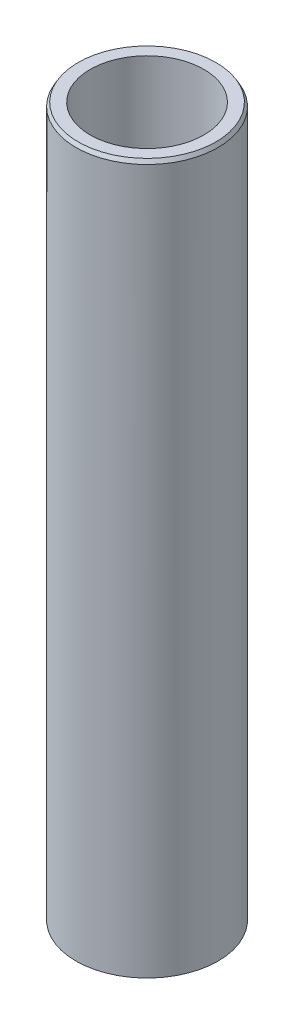
SolidWorks part; units mm, degrees
ref_plane "Front Plane" through (0, 0, 0) normal (0, 0, 1) x (1, 0, 0)
ref_plane "Top Plane" through (0, 0, 0) normal (0, 1, 0) x (1, 0, 0)
ref_plane "Right Plane" through (0, 0, 0) normal (1, 0, 0) x (0, 0, -1)
sketch "Sketch1" plane through (0, 0, 0) normal (0, 1, 0) x (1, 0, 0)
  circle A0 centre (0, 0) radius 60
  dimension "SHAFT_OD" = 120
extrude "Boss-Extrude1" add sketch "Sketch1" along normal blind 600
sketch "Sketch2" plane through (0, 0, 0) normal (0, 1, 0) x (1, 0, 0)
  circle A0 centre (0, 0) radius 48.0277
  dimension "BORE_D" = 96.0555
extrude "Cut-Extrude1" cut sketch "Sketch2" along normal through all
chamfer "Chamfer1" distance 3.1964 angle 30 2 edges at (0, 600, 60) (0, 0, 60) first distance on face at (0, 600, 60) first distance on face at (0, 0, 48.0277)
